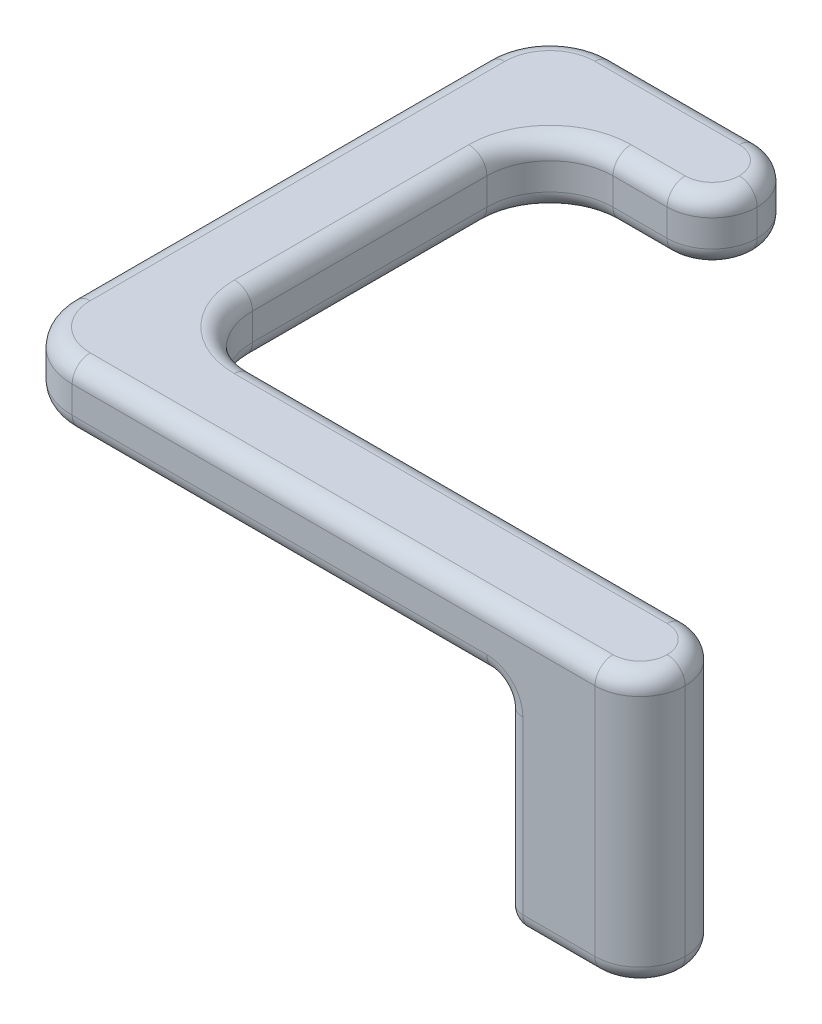
SolidWorks part; units mm, degrees
ref_plane "Front Plane" through (0, 0, 0) normal (0, 0, 1) x (1, 0, 0)
ref_plane "Top Plane" through (0, 0, 0) normal (0, 1, 0) x (1, 0, 0)
ref_plane "Right Plane" through (0, 0, 0) normal (1, 0, 0) x (0, 0, -1)
sketch "Sketch1" plane through (0, 0, 0) normal (0, 1, 0) x (1, 0, 0)
  line L0 (0, 0) -> (0, 20)
  line L1 (0, 20) -> (9, 20)
  line L2 (0, 0) -> (30, 0)
  point P2 (7.5, 15)
  dimension "D1" = 30
  dimension "D2" = 20
  dimension "D3" = 9
extrude "Extrude-Thin1" add sketch "Sketch1" along normal blind 15 thin thin type one direction wall 5
fillet "Fillet1" radius 2.5 4 edges at (30, 7.5, 5) (30, 7.5, 0) (9, 7.5, -20) (9, 7.5, -25)
fillet "Fillet2" radius 3.5 4 edges at (0, 7.5, 0) (-5, 7.5, 5) (-5, 7.5, -25) (0, 7.5, -20)
sketch "Sketch2" plane through (0, 0, 0) normal (0, -1, 0) x (1, 0, 0)
  line L1 (-22.5, 28.1932) -> (22.5, 28.1932)
  line L2 (-22.5, 28.1932) -> (-22.5, -28.1932)
  line L3 (-22.5, -28.1932) -> (22.5, -28.1932)
  line L4 (22.5, 28.1932) -> (22.5, -28.1932)
  line L5 (-22.5, 28.1932) -> (22.5, -28.1932) construction
  line L6 (-22.5, -28.1932) -> (22.5, 28.1932) construction
  point P0 (0, 0)
  dimension "D1" = 7.5
  dimension "D2" = 45
extrude "Cut-Extrude1" cut sketch "Sketch2" against normal blind 11.5
fillet "Fillet3" radius 1 34 edges at (22.5, 5.75, 5) (10.5, 11.5, 5) (-3.9749, 11.5, 3.9749) (-5, 11.5, -10) (-3.9749, 11.5, -23.9749) (2.5, 11.5, -25) (8.2678, 11.5, -24.2678) (8.2678, 11.5, -20.7322) (5, 11.5, -20) (1.0251, 11.5, -18.9749) (0, 11.5, -10) (1.0251, 11.5, -1.0251) (13, 11.5, 0) (5, 15, -20) (1.0251, 15, -18.9749) (0, 15, -10) (1.0251, 15, -1.0251) (15.5, 15, 0) (29.2678, 15, 0.7322) (29.2678, 15, 4.2678) (13, 15, 5) (-3.9749, 15, 3.9749) (-5, 15, -10) (-3.9749, 15, -23.9749) (2.5, 15, -25) (8.2678, 15, -24.2678) (25, 0, 5) (29.2678, 0, 4.2678) (29.2678, 0, 0.7322) (25, 0, 0) (22.5, 0, 2.5) (8.2678, 15, -20.7322) (22.5, 5.75, 0) (22.5, 11.5, 2.5)
